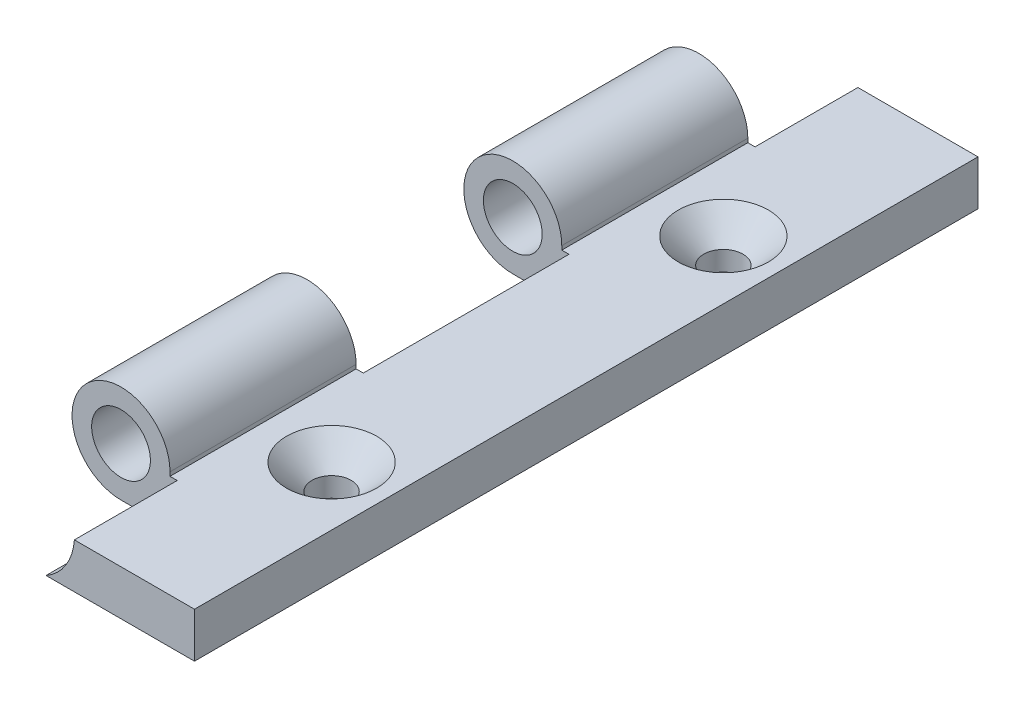
SolidWorks part; units mm, degrees
ref_plane "Front Plane" through (0, 0, 0) normal (0, 0, 1) x (1, 0, 0)
ref_plane "Top Plane" through (0, 0, 0) normal (0, 1, 0) x (1, 0, 0)
ref_plane "Right Plane" through (0, 0, 0) normal (1, 0, 0) x (0, 0, -1)
sketch "Sketch1" plane through (0, 0, 0) normal (0, 1, 0) x (1, 0, 0)
  line L1 (0, 0) -> (-9, 0)
  line L2 (0, 0) -> (0, 40)
  line L3 (0, 40) -> (-9, 40)
  line L4 (-9, 0) -> (-9, 40)
  dimension "D1" = 40
  dimension "D2" = 9
extrude "Boss-Extrude1" add sketch "Sketch1" along normal blind 2.5
sketch "Sketch2" plane through (0, 0, 0) normal (0, 0, 1) x (1, 0, 0)
  circle A0 centre (-9, 2.5) radius 2.5
extrude "Boss-Extrude2" add sketch "Sketch2" against normal blind 9.5 from offset 5.25 offset against normal yes
ref_plane "Plane1" through (0, 0, -20) normal (0, 0, 1) x (1, 0, 0)
sketch "Sketch3" plane through (0, 0, 0) normal (0, 0, 1) x (1, 0, 0)
  circle A0 centre (-9, 2.5) radius 1.5
  dimension "D1" = 3
extrude "Cut-Extrude1" cut sketch "Sketch3" against normal through all
sketch "Sketch4" plane through (0, 0, 0) normal (0, 0, 1) x (1, 0, 0)
  circle A0 centre (-9, 2.5) radius 2.875
  dimension "D1" = 5.75
extrude "Cut-Extrude2" cut sketch "Sketch4" against normal up to surface (5.25 mm away) up to face at (-9.2071, 2.7071, -5.25)
extrude "Cut-Extrude3" cut sketch "Sketch4<2>" along normal up to surface (-14.75 mm away) from surface up to face at (-9.2071, 2.7071, -14.75) starting at plane "Plane1"
sketch "Sketch4<2>" plane through (0, 0, 0) normal (0, 0, 1) x (1, 0, 0) same geometry as "Sketch4"
mirror "Mirror2" about plane through (0, 0, -20) normal (0, 0, 1) of "Cut-Extrude3", "Cut-Extrude2", "Cut-Extrude1", "Boss-Extrude2"
sketch "Sketch5" plane through (0, 2.5, 0) normal (0, 1, 0) x (1, 0, 0)
  line L0 (0, 0) -> (0, 40) construction
  line L1 (-6.125, 0) -> (0, 0) construction
  circle A0 centre (-3, 10) radius 1
  dimension "D1" = 2
  dimension "D2" = 3
  dimension "D3" = 10
extrude "Cut-Extrude4" cut sketch "Sketch5" against normal through all
mirror "Mirror3" about plane through (0, 0, -20) normal (0, 0, 1) of "Cut-Extrude4"
chamfer "Chamfer1" distance 1.5 angle 45 1 edges at (-3, 2.5, -31)
chamfer "Chamfer2" distance 1.5 angle 45 1 edges at (-3, 2.5, -9)
sketch "Sketch7" plane through (0, 0, 0) normal (0, 0, 1) x (1, 0, 0)
  line L0 (0, 2.5) -> (0, 0) construction
  line L1 (-6.5, 2.5) -> (0, 2.5)
  line L2 (-6.5, 2.5) -> (-6.5, 2.3)
  line L3 (-6.5, 2.3) -> (0, 2.3)
  line L4 (0, 2.5) -> (0, 2.3)
  dimension "D1" = 0.2
extrude "Cut-Extrude5" cut sketch "Sketch7" against normal through all
